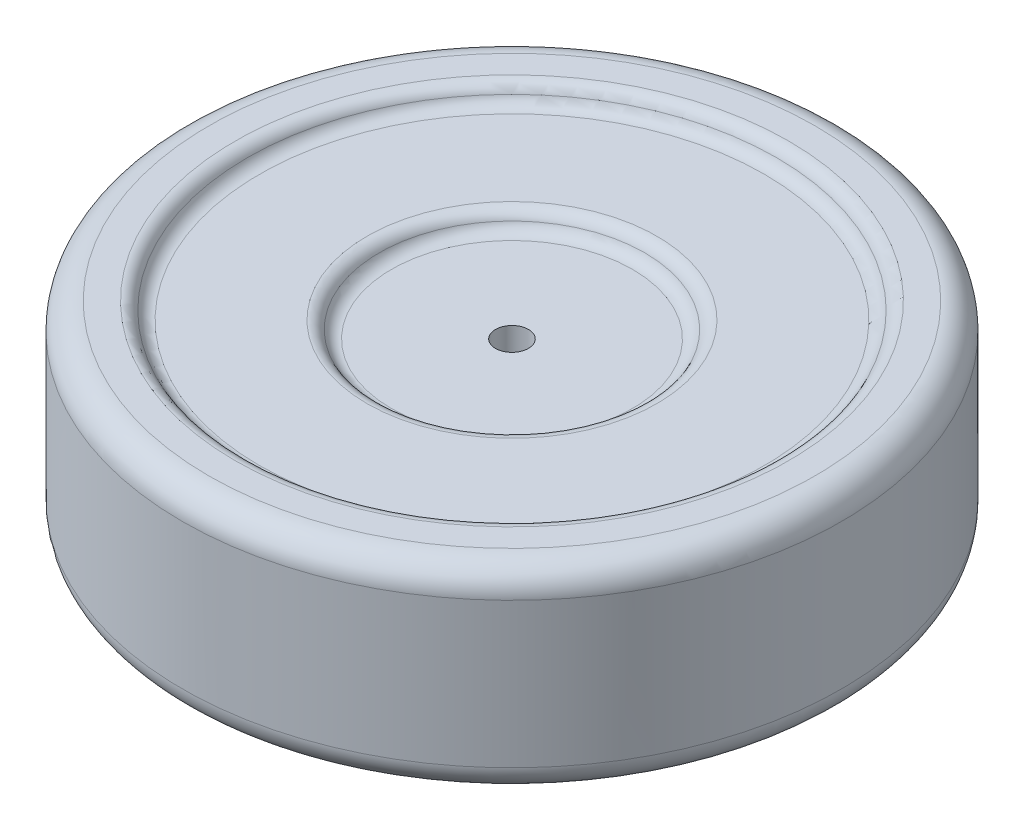
SolidWorks part; units mm, degrees
ref_plane "Front Plane" through (0, 0, 0) normal (0, 0, 1) x (1, 0, 0)
ref_plane "Top Plane" through (0, 0, 0) normal (0, 1, 0) x (1, 0, 0)
ref_plane "Right Plane" through (0, 0, 0) normal (1, 0, 0) x (0, 0, -1)
sketch "Sketch1" plane through (0, 0, 0) normal (0, 1, 0) x (1, 0, 0)
  circle A0 centre (0, 0) radius 127
extrude "Boss-Extrude1" add sketch "Sketch1" along normal blind 38.1
sketch "Sketch2" plane through (0, 38.1, 0) normal (0, 1, 0) x (1, 0, 0)
  circle A0 centre (0, 0) radius 101.6
extrude "Cut-Extrude1" cut sketch "Sketch2" against normal blind 6.35
sketch "Sketch3" plane through (0, 31.75, 0) normal (0, 1, 0) x (1, 0, 0)
  circle A0 centre (0, 0) radius 50.8
extrude "Cut-Extrude2" cut sketch "Sketch3" against normal blind 6.35
sketch "Sketch4" plane through (0, 25.4, 0) normal (0, 1, 0) x (1, 0, 0)
  circle A0 centre (0, 0) radius 6.35
extrude "Cut-Extrude3" cut sketch "Sketch4" against normal blind 77.978
fillet "Fillet1" radius 10.16 1 edges at (0, 38.1, 127)
fillet "Fillet2" radius 5.08 1 edges at (0, 38.1, 101.6)
fillet "Fillet3" radius 5.08 1 edges at (0, 31.75, 101.6)
fillet "Fillet4" radius 5.08 1 edges at (0, 31.75, 50.8)
fillet "Fillet5" radius 5.08 1 edges at (0, 25.4, 50.8)
mirror "Mirror1" about plane through (0, 0, 0) normal (0, 1, 0) of "Fillet5", "Fillet4", "Fillet3", "Fillet2", "Fillet1", "Cut-Extrude2", "Cut-Extrude3", "Cut-Extrude1", "Boss-Extrude1"
